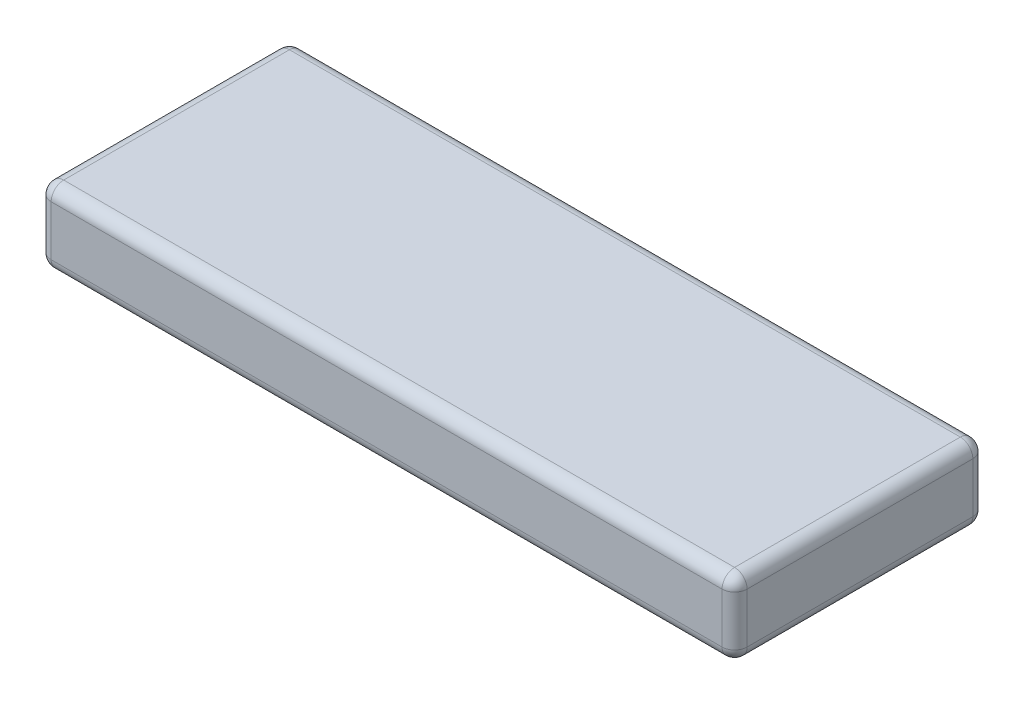
SolidWorks part; units mm, degrees
ref_plane "Plano frontal" through (0, 0, 0) normal (0, 0, 1) x (1, 0, 0)
ref_plane "Plano superior" through (0, 0, 0) normal (0, 1, 0) x (1, 0, 0)
ref_plane "Plano direito" through (0, 0, 0) normal (1, 0, 0) x (0, 0, -1)
sketch "Esboço1" plane through (0, 0, 0) normal (0, 1, 0) x (1, 0, 0)
  line L1 (0, 0) -> (111, 0)
  line L2 (0, 0) -> (0, 40)
  line L3 (0, 40) -> (111, 40)
  line L4 (111, 0) -> (111, 40)
  dimension "D1" = 111
  dimension "D2" = 40
extrude "Ressalto-extrusão1" add sketch "Esboço1" along normal blind 12
fillet "Filete1" radius 2 8 edges at (55.5, 0, 0) (111, 0, -20) (55.5, 0, -40) (0, 0, -20) (55.5, 12, -40) (111, 12, -20) (55.5, 12, 0) (0, 12, -20)
fillet "Filete2" radius 2 12 edges at (0.5858, 11.4142, -0.5858) (0.5858, 0.5858, -0.5858) (0.5858, 11.4142, -39.4142) (0.5858, 0.5858, -39.4142) (110.4142, 11.4142, -39.4142) (110.4142, 0.5858, -39.4142) (110.4142, 11.4142, -0.5858) (110.4142, 0.5858, -0.5858) (0, 6, 0) (0, 6, -40) (111, 6, -40) (111, 6, 0)
